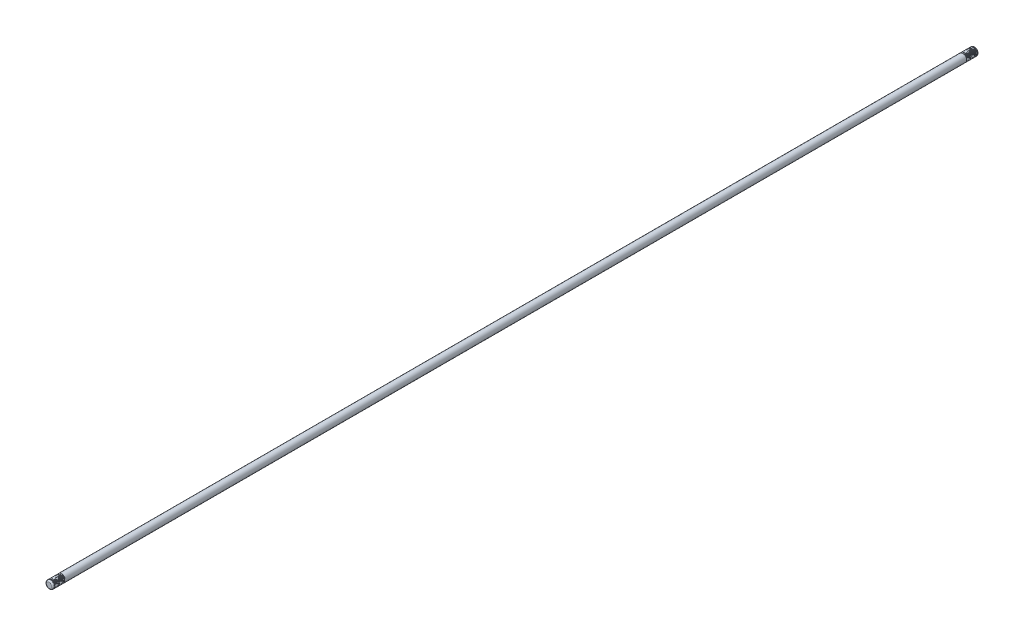
SolidWorks part; units mm, degrees
ref_plane "Plan de face" through (0, 0, 0) normal (0, 0, 1) x (1, 0, 0)
ref_plane "Plan de dessus" through (0, 0, 0) normal (0, 1, 0) x (1, 0, 0)
ref_plane "Plan de droite" through (0, 0, 0) normal (1, 0, 0) x (0, 0, -1)
sketch "Esquisse1" plane through (0, 0, 0) normal (0, 0, 1) x (1, 0, 0)
  circle A0 centre (0, 0) radius 3
extrude "Boss.-Extru.1" add sketch "Esquisse1" along normal blind 715
fillet "Congé1" radius 1 2 edges at (3, 0, 0) (3, 0, 715)
thread "Filetage1" pitch 0.7 method cut profile "Profil de filetage1" start angle 0, offset 0, length 8, pitch 0.7, diameter 6
ref_plane "Plan1" through (3, 0, 1) normal (0, -1, 0) x (1, 0, 0)
sketch "Profil de filetage1" plane through (3, 0, 1) normal (0, -1, 0) x (1, 0, 0)
  line L0 (0, 0) -> (0, 0.7) construction
  line L11 (0, 0) -> (0, 0.6125)
  line L12 (0, 0.6125) -> (-0.3789, 0.3937)
  line L13 (-0.3789, 0.3937) -> (-0.3789, 0.2187)
  line L15 (-0.3789, 0.2187) -> (0, 0)
  line L17 (-0.3789, 0.3062) -> (0, 0.3062) construction
  point P2 (0, 0)
  dimension "Pitch" = 0.7
  dimension "Profile_Angle" = 60
  dimension "Profile_Land" = 0.175
  dimension "Profile_Height" = 0.3789
thread "Filetage2" pitch 0.7 method cut profile "Profil de filetage2" start angle 0, offset 0, length 8, pitch 0.7, diameter 6
ref_plane "Plan2" through (-3, 0, 714) normal (0, -1, 0) x (-1, 0, 0)
sketch "Profil de filetage2" plane through (-3, 0, 714) normal (0, -1, 0) x (-1, 0, 0)
  line L0 (0, 0) -> (0, 0.7) construction
  line L11 (0, 0) -> (0, 0.6125)
  line L12 (0, 0.6125) -> (-0.3789, 0.3937)
  line L13 (-0.3789, 0.3937) -> (-0.3789, 0.2187)
  line L15 (-0.3789, 0.2187) -> (0, 0)
  line L17 (-0.3789, 0.3062) -> (0, 0.3062) construction
  point P2 (0, 0)
  dimension "Pitch" = 0.7
  dimension "Profile_Angle" = 60
  dimension "Profile_Land" = 0.175
  dimension "Profile_Height" = 0.3789
